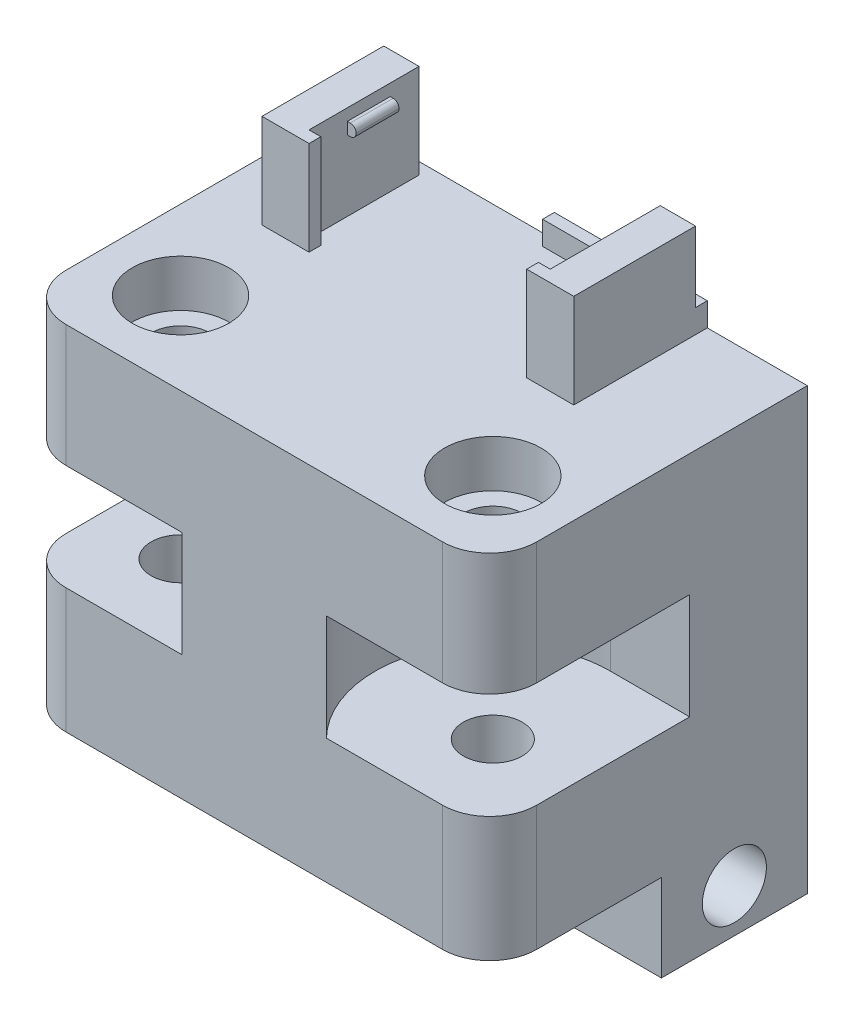
SolidWorks part; units mm, degrees
ref_plane "Front Plane" through (0, 0, 0) normal (0, 0, 1) x (1, 0, 0)
ref_plane "Top Plane" through (0, 0, 0) normal (0, 1, 0) x (1, 0, 0)
ref_plane "Right Plane" through (0, 0, 0) normal (1, 0, 0) x (0, 0, -1)
sketch "Sketch1" plane through (0, 0, 0) normal (0, 1, 0) x (1, 0, 0)
  line L1 (-22.8462, -9.1868) -> (17.1538, -9.1868)
  line L2 (-22.8462, -9.1868) -> (-22.8462, 17.8132)
  line L3 (-22.8462, 17.8132) -> (17.1538, 17.8132)
  line L4 (17.1538, -9.1868) -> (17.1538, 17.8132)
  dimension "D1" = 27
  dimension "D2" = 40
extrude "Boss-Extrude1" add sketch "Sketch1" along normal blind 30
sketch "Sketch2" plane through (0, 0, -17.8132) normal (0, 0, -1) x (-1, 0, 0)
  line L0 (2.8462, 30) -> (2.8462, 0) construction
  line L1 (-8.0864, 4) -> (-0.2064, 4)
  line L2 (-0.2064, 4) -> (-0.2064, 7)
  line L3 (-0.2064, 7) -> (-2.8664, 7)
  line L4 (-2.8664, 7) -> (-2.8664, 8.0087)
  line L5 (-2.8664, 8.0087) -> (-0.2538, 10.6287)
  line L6 (-0.2538, 10.6287) -> (5.9462, 10.6287)
  line L7 (-17.1538, 30) -> (22.8462, 30) construction
  line L8 (-17.1538, 0) -> (22.8462, 0) construction
  line L9 (-8.0864, 4) -> (-8.0864, 26)
  line L10 (-8.0864, 26) -> (-0.2064, 26)
  line L11 (-0.2064, 26) -> (-0.2064, 23)
  line L12 (-0.2064, 23) -> (-2.8664, 23)
  line L13 (-2.8664, 23) -> (-2.8664, 21.9913)
  line L14 (-2.8664, 21.9913) -> (-0.2464, 19.3787)
  line L15 (-0.2464, 19.3787) -> (5.9536, 19.3787)
  line L16 (-17.1538, 15) -> (22.8462, 15) construction
  line L17 (-17.1538, 30) -> (-17.1538, 0) construction
  line L18 (22.8462, 30) -> (22.8462, 0) construction
  line L19 (5.9387, 19.3787) -> (-0.2613, 19.3787)
  line L20 (8.5587, 21.9913) -> (5.9387, 19.3787)
  line L21 (8.5587, 23) -> (8.5587, 21.9913)
  line L22 (5.8987, 23) -> (8.5587, 23)
  line L23 (5.8987, 26) -> (5.8987, 23)
  line L24 (13.7787, 26) -> (5.8987, 26)
  line L25 (13.7787, 4) -> (13.7787, 26)
  line L26 (8.5587, 8.0087) -> (5.9462, 10.6287)
  line L27 (8.5587, 7) -> (8.5587, 8.0087)
  line L28 (5.8987, 7) -> (8.5587, 7)
  line L29 (5.8987, 4) -> (5.8987, 7)
  line L30 (13.7787, 4) -> (5.8987, 4)
  point P26 (-8.0864, 15)
  point P27 (2.8462, 15)
  point P37 (2.8462, 10.6287)
  dimension "D1" = 6.2
  dimension "D2" = 2.62
  dimension "D3" = 3.7
  dimension "D4" = 8.75
  dimension "D5" = 7.88
  dimension "D6" = 22
  dimension "D7" = 5.22
  dimension "D8" = 3
  dimension "D9" = 90
extrude "Cut-Extrude1" cut sketch "Sketch2" against normal blind 10 contours L30 L25 L24 L23 L22 L21 L20 L15 L14 L13 L12 L11 L10 L9 L1 L2 L3 L4 L5 L6 L26 L27 L28 L29 region at (-2.8462, 15.0011, -17.8132)
sketch "Sketch3" plane through (0, 0, 0) normal (0, -1, 0) x (1, 0, 0)
  line L0 (-22.8462, 9.1868) -> (17.1538, 9.1868) construction
  line L1 (17.1538, 9.1868) -> (17.1538, -17.8132) construction
  line L2 (-2.8462, 9.1868) -> (-2.8462, -17.8132) construction
  line L3 (17.1538, -17.8132) -> (-22.8462, -17.8132) construction
  circle A0 centre (10.4238, 2.1868) radius 2.5
  circle A2 centre (-16.1162, 2.1868) radius 2.5
  dimension "D1" = 5
  dimension "D3" = 7
  dimension "D4" = 6.73
extrude "Cut-Extrude2" cut sketch "Sketch3" against normal blind 30
sketch "Sketch8" plane through (0, 0, 0) normal (0, -1, 0) x (1, 0, 0)
  line L0 (3.2824, 9.1868) -> (17.1538, 9.1868)
  line L1 (-22.8462, 9.1868) -> (17.1538, 9.1868) construction
  line L2 (17.1538, 9.1868) -> (17.1538, -7.8132)
  line L3 (17.1538, 9.1868) -> (17.1538, -17.8132) construction
  line L4 (17.1538, -7.8132) -> (10.4238, -7.8132)
  line L6 (-2.8462, -17.8132) -> (-2.8462, 9.1868) construction
  line L7 (17.1538, -17.8132) -> (-22.8462, -17.8132) construction
  line L8 (-22.8462, -7.8132) -> (-16.1162, -7.8132)
  line L9 (-22.8462, 9.1868) -> (-22.8462, -7.8132)
  line L10 (-8.9747, 9.1868) -> (-22.8462, 9.1868)
  arc A0 (10.4238, -7.8132) -> (3.2824, 9.1868) centre (10.4238, 2.1868) cw
  arc A1 (-16.1162, -7.8132) -> (-8.9747, 9.1868) centre (-16.1162, 2.1868) ccw
  circle M6 centre (10.4238, 2.1868) radius 2.5
  circle M7 centre (-16.1162, 2.1868) radius 2.5
  line M8 (-22.8462, 9.1868) -> (-22.8462, -17.8132)
  line M10 (17.1538, -17.8132) -> (17.1538, 9.1868)
  line M11 (17.1538, 9.1868) -> (-22.8462, 9.1868)
  dimension "D1" = 10
extrude "Cut-Extrude5" cut sketch "Sketch8" against normal blind 9 from offset 10.62 contours A0 L4 M10 M11 M6 | M6 | L8 A1 M11 M8 M7 | M7 region at (10.2181, 0, 8.9483) region at (-7.1165, 0, -1.5938) region at (10.4238, 0, 2.1868) region at (-16.1162, 0, 2.1868) offset against normal yes
sketch "Sketch10" plane through (8.0864, 0, 0) normal (-1, 0, 0) x (0, 0, 1)
  line L0 (-17.8132, 30) -> (-17.8132, 0) construction
  line L1 (-17.8132, 19.62) -> (2.1868, 19.62)
  line L2 (-17.8132, 19.62) -> (-17.8132, 10.62)
  line L3 (-17.8132, 10.62) -> (2.1868, 10.62)
  line L4 (2.1868, 19.62) -> (2.1868, 10.62)
  line L6 (-7.8132, 19.62) -> (9.1868, 19.62) construction
  dimension "D1" = 20
extrude "Cut-Extrude7" cut sketch "Sketch10" along normal blind 6.8
sketch "Sketch12" plane through (-13.7787, 0, 0) normal (1, 0, 0) x (0, 0, -1)
  line L3 (17.8132, 10.62) -> (-2.1868, 10.62)
  line L6 (-2.1868, 10.62) -> (-2.1868, 19.62)
  line L7 (7.8132, 19.62) -> (-9.1868, 19.62) construction
  line L8 (-2.1868, 19.62) -> (17.8132, 19.62)
  line L9 (17.8132, 30) -> (17.8132, 0) construction
  line L10 (17.8132, 19.62) -> (17.8132, 10.62)
extrude "Cut-Extrude10" cut sketch "Sketch12" along normal blind 6.8
fillet "Fillet1" radius 4 4 edges at (17.1538, 5.31, 9.1868) (17.1538, 24.81, 9.1868) (-22.8462, 5.31, 9.1868) (-22.8462, 24.81, 9.1868)
sketch "Sketch13" plane through (17.1538, 0, 0) normal (1, 0, 0) x (0, 0, -1)
  line L0 (-5.1868, 0) -> (17.8132, 0) construction
  line L1 (17.8132, 30) -> (17.8132, 0) construction
  line L3 (17.8132, 0) -> (5.4132, 0)
  line L4 (17.8132, 0) -> (17.8132, -7.4)
  line L5 (17.8132, -7.4) -> (5.4132, -7.4)
  line L6 (5.4132, 0) -> (5.4132, -7.4)
  circle A0 centre (11.6132, -3.7) radius 2.725
  dimension "D1" = 6.2
  dimension "D2" = 3.7
  dimension "D3" = 5.45
  dimension "D4" = 12.4
  dimension "D5" = 7.4
extrude "Boss-Extrude2" add sketch "Sketch13" against normal up to surface (40 mm away) up to face at (-22.8462, 15.06, -3.8132)
sketch "Sketch14" plane through (0, 0, -5.4132) normal (0, 0, 1) x (1, 0, 0)
  line L0 (-22.8462, -7.4) -> (17.1538, -7.4) construction
  line L1 (-12.8462, -7.4) -> (7.1538, -7.4)
  line L2 (-12.8462, -7.4) -> (-12.8462, 0)
  line L3 (-12.8462, 0) -> (7.1538, 0)
  line L4 (7.1538, -7.4) -> (7.1538, 0)
  line L5 (-18.8462, 0) -> (13.1538, 0) construction
  line L7 (17.1538, 0) -> (17.1538, -7.4) construction
  dimension "D1" = 20
  dimension "D2" = 10
extrude "Cut-Extrude11" cut sketch "Sketch14" against normal up to next
sketch "Sketch15" plane through (0, 30, 0) normal (0, 1, 0) x (1, 0, 0)
  line L0 (-2.8462, 17.8132) -> (-2.8462, -9.1868) construction
  line L13 (17.1538, 17.8132) -> (-22.8462, 17.8132) construction
  line L14 (-18.8462, -9.1868) -> (13.1538, -9.1868) construction
  circle A4 centre (-16.1162, -2.1868) radius 4.1
  circle A5 centre (10.4238, -2.1868) radius 4.1
  dimension "D1" = 8.2
extrude "Cut-Extrude12" cut sketch "Sketch15" against normal blind 4
sketch "Sketch16" plane through (0, 0, 0) normal (0, -1, 0) x (1, 0, 0)
  line L1 (-13.749, -1.9132) -> (-11.3819, 2.1868)
  line L2 (-11.3819, 2.1868) -> (-13.749, 6.2868)
  line L3 (-13.749, 6.2868) -> (-18.4833, 6.2868)
  line L4 (-18.4833, 6.2868) -> (-20.8504, 2.1868)
  line L5 (-20.8504, 2.1868) -> (-18.4833, -1.9132)
  line L6 (-18.4833, -1.9132) -> (-13.749, -1.9132)
  line L7 (12.791, -1.9132) -> (15.1581, 2.1868)
  line L8 (15.1581, 2.1868) -> (12.791, 6.2868)
  line L9 (12.791, 6.2868) -> (8.0567, 6.2868)
  line L10 (8.0567, 6.2868) -> (5.6896, 2.1868)
  line L11 (5.6896, 2.1868) -> (8.0567, -1.9132)
  line L12 (8.0567, -1.9132) -> (12.791, -1.9132)
  circle A0 centre (10.4238, 2.1868) radius 2.5 construction
  circle A1 centre (-16.1162, 2.1868) radius 2.5 construction
  circle A2 centre (10.4238, 2.1868) radius 2.5
  circle A3 centre (-16.1162, 2.1868) radius 2.5
  circle A4 centre (-16.1162, 2.1868) radius 4.1 construction
  circle A5 centre (10.4238, 2.1868) radius 4.1 construction
  dimension "D1" = 8.2
  dimension "D2" = 8.2
extrude "Cut-Extrude13" cut sketch "Sketch16" against normal blind 4
sketch "Sketch17" plane through (0, 30, 0) normal (0, 1, 0) x (1, 0, 0)
  line L1 (8.6538, 16.8132) -> (5.6538, 16.8132)
  line L2 (8.6538, 16.8132) -> (8.6538, 7.4632)
  line L3 (8.6538, 7.4632) -> (5.6538, 7.4632)
  line L4 (-18.8462, -9.1868) -> (13.1538, -9.1868)
  line L5 (17.1538, -5.1868) -> (17.1538, 17.8132)
  line L6 (17.1538, 17.8132) -> (-22.8462, 17.8132)
  line L7 (-22.8462, 17.8132) -> (-22.8462, -5.1868)
  line L8 (-18.8462, -9.1868) -> (13.1538, -9.1868)
  line L9 (17.1538, -5.1868) -> (17.1538, 17.8132)
  line L10 (17.1538, 17.8132) -> (-22.8462, 17.8132)
  line L11 (-22.8462, 17.8132) -> (-22.8462, -5.1868)
  line L12 (5.6538, 16.8132) -> (5.6538, 7.4632)
  line L13 (-14.8462, 16.8132) -> (-17.8462, 16.8132)
  line L14 (-14.8462, 16.8132) -> (-14.8462, 7.4632)
  line L15 (-14.8462, 7.4632) -> (-17.8462, 7.4632)
  line L16 (-17.8462, 16.8132) -> (-17.8462, 7.4632)
  line L17 (8.6538, 7.4632) -> (4.6538, 7.4632)
  line L18 (8.6538, 7.4632) -> (8.6538, 6.4632)
  line L19 (8.6538, 6.4632) -> (4.6538, 6.4632)
  line L20 (4.6538, 7.4632) -> (4.6538, 6.4632)
  line L21 (-17.8462, 7.4632) -> (-13.8462, 7.4632)
  line L22 (-17.8462, 7.4632) -> (-17.8462, 6.4632)
  line L23 (-17.8462, 6.4632) -> (-13.8462, 6.4632)
  line L24 (-13.8462, 7.4632) -> (-13.8462, 6.4632)
  arc A2 (13.1538, -9.1868) -> (17.1538, -5.1868) centre (13.1538, -5.1868) ccw
  arc A3 (-22.8462, -5.1868) -> (-18.8462, -9.1868) centre (-18.8462, -5.1868) ccw
  arc A4 (13.1538, -9.1868) -> (17.1538, -5.1868) centre (13.1538, -5.1868) ccw
  arc A5 (-22.8462, -5.1868) -> (-18.8462, -9.1868) centre (-18.8462, -5.1868) ccw
  line M30 (17.1538, 17.8132) -> (-22.8462, 17.8132)
  dimension "D2" = 9.35
  dimension "D3" = 3
  dimension "D4" = 3
  dimension "D5" = 20.5
  dimension "D6" = 5
  dimension "D7" = 1
  dimension "D8" = 1
  dimension "D9" = 4
  dimension "D10" = 1
  dimension "D11" = 1
  dimension "D1" = 0
extrude "Boss-Extrude3" add sketch "Sketch17" along normal blind 8 contours L12 L3 L2 M30 | L10 L16 L15 L14 | L24 L21 L15 L22 L23 | L17 L20 L19 L18 L3 region at (7.1538, 30, -12.1382) region at (6.6538, 30, -6.9632) region at (-16.3462, 30, -12.1382) region at (-15.8462, 30, -6.9632)
sketch "Sketch20" plane through (0, 38, 0) normal (0, 1, 0) x (1, 0, 0)
  line L0 (5.6538, 16.8132) -> (5.6538, 7.4632) construction
  line L1 (5.6538, 14.3623) -> (4.9038, 14.3623)
  line L2 (5.6538, 14.3623) -> (5.6538, 10.716)
  line L3 (5.6538, 10.716) -> (4.9038, 10.716)
  line L4 (4.9038, 14.3623) -> (4.9038, 10.716)
  line L5 (-14.8462, 16.8132) -> (-14.8462, 7.4632) construction
  line L6 (-14.8462, 14.3623) -> (-14.0962, 14.3623)
  line L7 (-14.8462, 14.3623) -> (-14.8462, 10.716)
  line L8 (-14.8462, 10.716) -> (-14.0962, 10.716)
  line L9 (-14.0962, 14.3623) -> (-14.0962, 10.716)
  dimension "D1" = 0.75
  dimension "D2" = 0.75
extrude "Boss-Extrude4" add sketch "Sketch20" along normal blind 1 from offset 2 offset against normal yes
fillet "Fillet2" radius 0.5 4 edges at (-14.0962, 36, -12.5391) (4.9038, 36, -12.5391) (-14.0962, 37, -12.5391) (4.9038, 37, -12.5391)
sketch "Sketch22" plane through (0, 0, -17.8132) normal (0, 0, -1) x (-1, 0, 0)
  line L1 (-8.6538, 32) -> (4.3462, 32)
  line L2 (-8.6538, 32) -> (-8.6538, 30)
  line L3 (-8.6538, 30) -> (4.3462, 30)
  line L4 (4.3462, 32) -> (4.3462, 30)
  line L7 (-5.6538, 38) -> (-5.6538, 30) construction
  line L8 (-5.6538, 38) -> (-5.6538, 30)
  line L9 (-17.1538, 30) -> (22.8462, 30) construction
  line L11 (-8.6538, 38) -> (-8.6538, 30) construction
  dimension "D1" = 2
  dimension "D2" = 13
extrude "Boss-Extrude6" add sketch "Sketch22" along normal blind 1 from surface contours L8 L1 L2 L3 | L1 L8 L3 L4 region at (7.1538, 31, -17.8132) region at (0.6538, 31, -17.8132) starting at face at (7.1538, 34, -16.8132)
